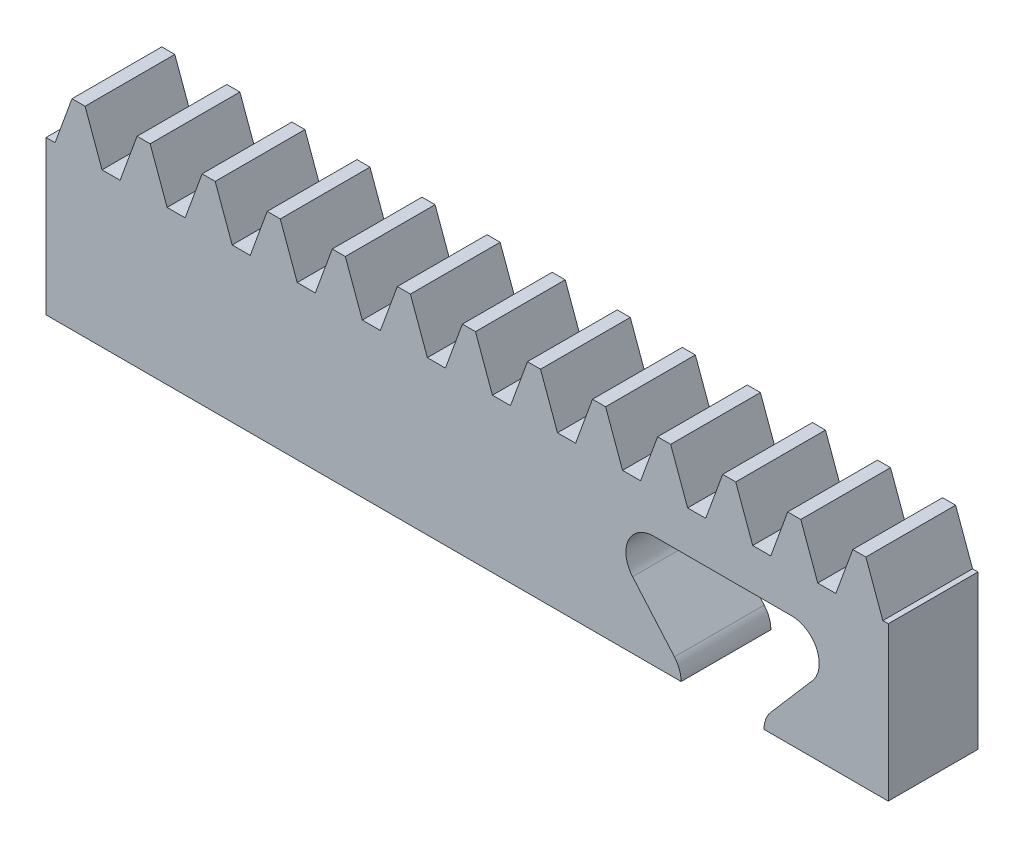
SolidWorks part; units mm, degrees
extrude "Blank" add sketch "BlankSke" against normal blind 6.5
sketch "BlankSke" plane through (0, 0, 0) normal (0, 0, 1) x (1, 0, 0)
  line L1 (0, 0) -> (61, 0)
  line L2 (0, 0) -> (0, 14.5)
  line L3 (0, 14.5) -> (61, 14.5)
  line L4 (61, 0) -> (61, 14.5)
  dimension "Length" = 61
ref_plane "Plane1" through (0, 0, 0) normal (0, 0, 1) x (1, 0, 0)
ref_plane "Plane2" through (0, 0, 0) normal (0, 1, 0) x (1, 0, 0)
ref_plane "Plane3" through (0, 0, 0) normal (1, 0, 0) x (0, 0, -1)
other "Configuration Table"
sketch "HoldingSke" plane through (0, 0, 0) normal (0, 1, 0) x (1, 0, 0)
  line L0 (0, 0) -> (0.0928, 0.6602)
  line L1 (-15, 0) -> (100, 0) construction
  line L2 (0, 0) -> (-2.1039, 2.3779)
  line L3 (0, 0) -> (-11.863, 4.5341)
  line L4 (0, 0) -> (8.3795, 2.0892)
  line L5 (0, 0) -> (-23.7986, -8.8762)
  line L6 (0, 0) -> (-10.5278, -7.1032)
  line L9 (-71.009, 38.7566) -> (-13.6877, 59.6198)
  line L10 (-76.2, 3.8779) -> (-63.2, 3.8779)
  line L11 (0, 0) -> (-6.5, 0)
  line L12 (-76.2, 101.6) -> (-76.147, 101.6)
  line L13 (24.9733, 27.94) -> (52.9518, 28.4284)
  line L14 (24.9733, 27.94) -> (24.9743, 27.94)
  line L15 (24.9733, 27.94) -> (100.4006, 29.5858)
  circle A0 centre (0, 0) radius 19.05
  circle A1 centre (0, 0) radius 6.5
  circle A2 centre (0, 0) radius 12.7
  dimension "Num_teeth" = 14
  dimension "Width" = 6.5
  dimension "Length" = 61
  dimension "Pitch_height" = 13
sketch "TooCutSkeIll" plane through (0, 0, 0) normal (0, 0, 1) x (1, 0, 0)
  line L0 (-1.8687, 14.4605) -> (-0.7447, 11.3724)
  line L1 (-0.3914, 11.125) -> (0.3914, 11.125)
  line L2 (0.7447, 11.3724) -> (1.8687, 14.4605)
  line L3 (61, 14.5) -> (0, 14.5) construction
  line L4 (0, 0) -> (0, 64.897) construction
  line L5 (-13.208, 13) -> (12.954, 13) construction
  line L6 (0, 0) -> (61, 0) construction
  line L7 (1.3371, 13) -> (1.3371, 48.7463) construction
  line L8 (-1.3371, 13) -> (-1.3371, 48.7463) construction
  line L9 (1.9251, 14.5) -> (1.9251, 14.5254)
  line L10 (-1.9251, 14.5) -> (-1.9251, 14.5254)
  line L11 (-1.9251, 14.5254) -> (1.9251, 14.5254)
  arc A0 (0.3914, 11.125) -> (0.7447, 11.3724) centre (0.3914, 11.501) ccw
  arc A1 (-0.7447, 11.3724) -> (-0.3914, 11.125) centre (-0.3914, 11.501) ccw
  arc A2 (1.9251, 14.5) -> (1.8687, 14.4605) centre (1.9251, 14.44) ccw
  arc A3 (-1.8687, 14.4605) -> (-1.9251, 14.5) centre (-1.9251, 14.44) ccw
  dimension "Addendum_plus" = 1.5254
  dimension "Pitch_height" = 13
  dimension "Pressure_angle" = 20
  dimension "Gap_width" = 2.6742
  dimension "Dedendum" = 1.875
extrude "ToothCutIll" [suppressed] cut sketch "TooCutSkeIll" against normal through all
sketch "TooCutSkeSim" plane through (0, 0, 0) normal (0, 0, 1) x (1, 0, 0)
  line L0 (0.6547, 11.125) -> (-0.6547, 11.125)
  line L1 (1.8923, 14.5254) -> (0.6547, 11.125)
  line L2 (0, 17.4625) -> (0, 53.467) construction
  line L3 (1.8923, 14.5254) -> (-1.8923, 14.5254)
  line L6 (-1.8923, 14.5254) -> (-0.6547, 11.125)
  line L9 (-1.3371, 13) -> (1.3371, 13) construction
  line L10 (0, 0) -> (61, 0) construction
  line L11 (1.3371, 13) -> (1.3371, 53.467) construction
  line L12 (-1.3371, 13) -> (-1.3371, 53.467) construction
  dimension "Addendum_plus" = 1.5254
  dimension "Pitch_height" = 13
  dimension "Pressure_angle" = 20
  dimension "Gap_width" = 2.6742
  dimension "Dedendum" = 1.875
extrude "ToothCutSim" cut sketch "TooCutSkeSim" against normal through all
pattern_linear "TeethCuts" count 14 spacing 4.7124 along (1, 0, 0) of "ToothCutIll", "ToothCutSim"
sketch "Sketch1" plane through (0, 0, -6.5) normal (0, 0, -1) x (-1, 0, 0)
  line L0 (-49, 0) -> (-49, 8.8731) construction
  line L1 (0, 0) -> (-61, 0) construction
  line L2 (-44, 8.125) -> (-54, 8.125)
  line L3 (-55.5146, 4.8189) -> (-52.4854, 1.3061)
  line L4 (-42.4854, 4.8189) -> (-45.5146, 1.3061)
  line L5 (-46, 0) -> (-52, 0)
  line L6 (-61, 0) -> (-61, 11.125) construction
  line L7 (-46.4692, 11.125) -> (-47.7785, 11.125) construction
  arc A0 (-54, 8.125) -> (-55.5146, 4.8189) centre (-54, 6.125) ccw
  arc A1 (-44, 8.125) -> (-42.4854, 4.8189) centre (-44, 6.125) cw
  arc A2 (-52, 0) -> (-52.4854, 1.3061) centre (-54, 0) ccw
  arc A3 (-46, 0) -> (-45.5146, 1.3061) centre (-44, 0) cw
  point P7 (-49, 8.125)
  point P16 (0, 0)
  point P17 (-48.9121, 0)
  point P22 (-49, 0)
  dimension "D1" = 2
  dimension "D2" = 2
  dimension "D3" = 10
  dimension "D4" = 12
  dimension "D5" = 6
  dimension "D6" = 3
  dimension "D7" = 8.125
extrude "Cut-Extrude1" cut sketch "Sketch1" against normal up to surface (6.5 mm away) up to face at (30.6212, 12.2946, 0)
equation "' \"Module@HoldingSke\" = 6.35"
equation "' \"Num_teeth@HoldingSke\" = 12"
equation "' \"Ap@HoldingSke\" =  20"
equation "' \"Ap@HoldingSke\" = 20"
equation "' \"Width@HoldingSke\" = 0.25 * 25.4"
equation "' \"Show_teeth@HoldingSke\" = 500"
equation "' \"Backlash@HoldingSke\" = 0.009 * 25.4"
equation "' \"Addendum_fac@HoldingSke\" = 1.0"
equation "' \"Dedendum_fac@HoldingSke\" = 1.25"
equation "' \"Dedendum_add@HoldingSke\" = 0.00005 * 25.4"
equation "' \"Clearance_fac@HoldingSke\" = 0.25"
equation "' \"Pitch_height@HoldingSke\" = 1 * 25.4"
equation "' \"Length@HoldingSke\" = 4.71 * 25.4"
equation "\"Pitch@HoldingSke\" = 1 / \"Module@HoldingSke\""
equation "\"MPH@HoldingSke\" = \"Dedendum_fac@HoldingSke\" / \"Pitch@HoldingSke\" + 2 * \"Dedendum_add@HoldingSke\" + 0.002 * 25.4"
equation "\"MPH@HoldingSke\" = ((sgn( \"MPH@HoldingSke\" - \"Pitch_height@HoldingSke\")+1)*( \"MPH@HoldingSke\" - \"Pitch_height@HoldingSke\"))/2 + \"Pitch_height@HoldingSke\""
equation "\"Blank_height@BlankSke\" = \"Pitch_height@HoldingSke\" + \"Addendum_fac@HoldingSke\"  / \"Pitch@HoldingSke\" "
equation "\"Length@BlankSke\" =  \"Length@HoldingSke\""
equation "\"Face_width@Blank\" = \"Width@HoldingSke\""
equation "\"Pressure_angle@TooCutSkeIll\" = \"Ap@HoldingSke\""
equation "\"Addendum_plus@TooCutSkeIll\" =  \"Addendum_fac@HoldingSke\"  / \"Pitch@HoldingSke\" + 0.001 *25.4"
equation "\"Dedendum@TooCutSkeIll\" = \"Dedendum_fac@HoldingSke\"  / \"Pitch@HoldingSke\""
equation "\"Pitch_height@TooCutSkeIll\" =  \"MPH@HoldingSke\""
equation "\"Gap_width@TooCutSkeIll\" = 3.14159265 / 2 / \"Pitch@HoldingSke\" + 6 * \"Backlash@HoldingSke\""
equation "\"Pressure_angle@TooCutSkeSim\" = \"Ap@HoldingSke\""
equation "\"Addendum_plus@TooCutSkeSim\" =  \"Addendum_fac@HoldingSke\"  / \"Pitch@HoldingSke\" + 0.001 * 25.4"
equation "\"Dedendum@TooCutSkeSim\" = \"Dedendum_fac@HoldingSke\"  / \"Pitch@HoldingSke\""
equation "\"Pitch_height@TooCutSkeSim\" =  \"MPH@HoldingSke\""
equation "\"Gap_width@TooCutSkeSim\" = 3.14159265 / 2 / \"Pitch@HoldingSke\" + 6 * \"Backlash@HoldingSke\""
equation "\"Root_fillet@TooCutSkeIll\" = \"Clearance_fac@HoldingSke\" / \"Pitch@HoldingSke\" + \"Dedendum_add@HoldingSke\""
equation "\"Break_rad@TooCutSkeIll\" = 0.02 / \"Pitch@HoldingSke\" * 2"
equation "\"Linear_pitch@TeethCuts\" = 3.14159265 / \"Pitch@HoldingSke\""
equation "\"Num_teeth@HoldingSke\" = int( ( \"Length@HoldingSke\" + 0 ) / (3.14159265 / \"Pitch@HoldingSke\")) + 0.9999  + 1"
equation " \"Num_teeth@TeethCuts\" = int( \"Show_teeth@HoldingSke\" ) + 1"
equation " \"Num_teeth@TeethCuts\" = ((sgn( \"Num_teeth@TeethCuts\" - \"Num_teeth@HoldingSke\" )-1)*( \"Num_teeth@TeethCuts\" - \"Num_teeth@HoldingSke\" ))/-2+ \"Num_teeth@HoldingSke\""
equation " \"Num_teeth@TeethCuts\" = ((sgn( \"Num_teeth@TeethCuts\" - 2.0)+1)*( \"Num_teeth@TeethCuts\" - 2.0))/2 +2.0"
